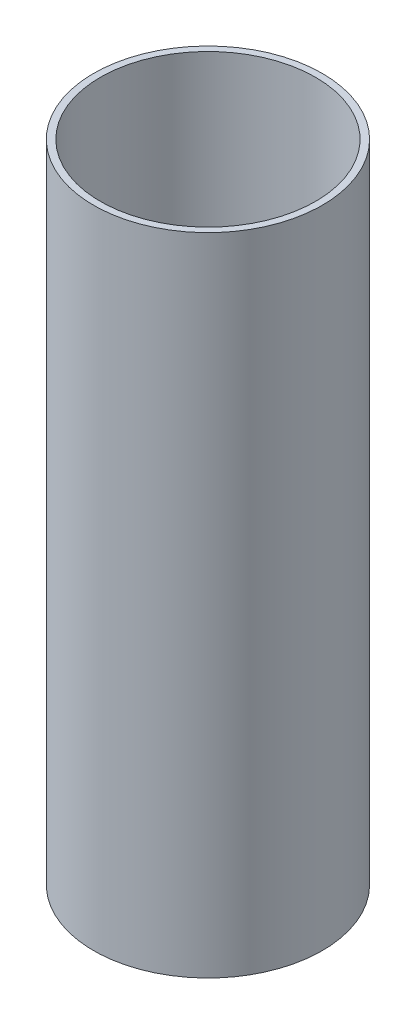
SolidWorks part; units mm, degrees
material "E-Glass Fiber"
ref_plane "Front Plane" through (0, 0, 0) normal (0, 0, 1) x (1, 0, 0)
ref_plane "Top Plane" through (0, 0, 0) normal (0, 1, 0) x (1, 0, 0)
ref_plane "Right Plane" through (0, 0, 0) normal (1, 0, 0) x (0, 0, -1)
sketch "Sketch1" plane through (0, 0, 0) normal (0, 0, 1) x (1, 0, 0)
  line L0 (0, 0) -> (0, 53.3818) construction
  line L1 (-26.9875, 50.506) -> (26.9875, 50.506) construction
  line L2 (25.4, 50.506) -> (26.9875, 50.506)
  line L3 (25.4, 50.506) -> (25.4, -101.894)
  line L4 (25.4, -101.894) -> (26.9875, -101.894)
  line L5 (26.9875, 50.506) -> (26.9875, -101.894)
  line L6 (26.9875, 50.506) -> (26.9875, -101.894) construction
  point P7 (21.2032, 50.506)
  point P10 (26.9875, 50.506)
  point P12 (26.9875, -19.244)
  point P15 (26.9875, -101.894)
  dimension "D1" = 1.5875
revolve "Revolve1" add sketch "Sketch1" angle 360 about L0
